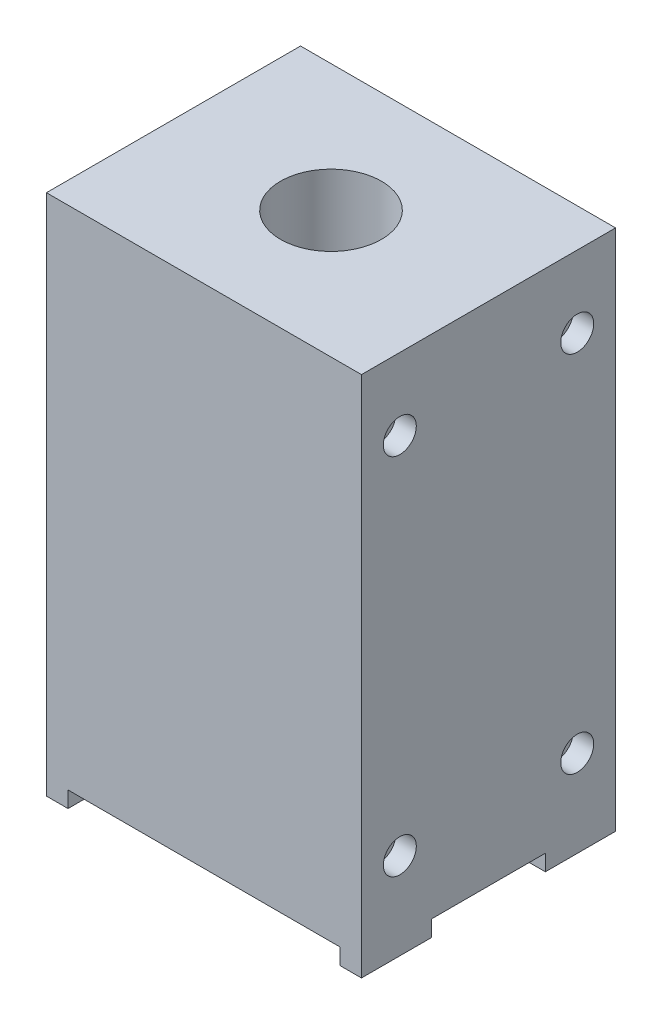
SolidWorks part; units mm, degrees
ref_plane "Front Plane" through (0, 0, 0) normal (0, 0, 1) x (1, 0, 0)
ref_plane "Top Plane" through (0, 0, 0) normal (0, 1, 0) x (1, 0, 0)
ref_plane "Right Plane" through (0, 0, 0) normal (1, 0, 0) x (0, 0, -1)
sketch "Sketch2" plane through (0, 0, 0) normal (0, 1, 0) x (1, 0, 0)
  line L1 (-15.325, 12.36) -> (15.325, 12.36)
  line L2 (-15.325, 12.36) -> (-15.325, -12.36)
  line L3 (-15.325, -12.36) -> (15.325, -12.36)
  line L4 (15.325, 12.36) -> (15.325, -12.36)
  line L5 (-15.325, 12.36) -> (15.325, -12.36) construction
  line L6 (-15.325, -12.36) -> (15.325, 12.36) construction
  point P0 (0, 0)
  dimension "D1" = 24.72
  dimension "D2" = 30.65
extrude "Boss-Extrude1" add sketch "Sketch2" along normal blind 49.27
sketch "Sketch12" plane through (0, 0, 0) normal (0, -1, 0) x (1, 0, 0)
  line L1 (-15.325, 12.36) -> (-13.225, 12.36)
  line L2 (-15.325, 12.36) -> (-15.325, 5.53)
  line L3 (-15.325, 5.53) -> (-13.225, 5.53)
  line L4 (-13.225, 12.36) -> (-13.225, 5.53)
  line L5 (-15.325, -12.36) -> (-13.225, -12.36)
  line L6 (-15.325, -12.36) -> (-15.325, -5.53)
  line L7 (-15.325, -5.53) -> (-13.225, -5.53)
  line L8 (-13.225, -12.36) -> (-13.225, -5.53)
  line L9 (15.325, 12.36) -> (13.225, 12.36)
  line L10 (15.325, 12.36) -> (15.325, 5.53)
  line L11 (15.325, 5.53) -> (13.225, 5.53)
  line L12 (13.225, 12.36) -> (13.225, 5.53)
  line L13 (15.325, -12.36) -> (13.225, -12.36)
  line L14 (15.325, -12.36) -> (15.325, -5.53)
  line L15 (15.325, -5.53) -> (13.225, -5.53)
  line L16 (13.225, -12.36) -> (13.225, -5.53)
  dimension "D1" = 6.83
  dimension "D2" = 6.83
  dimension "D3" = 6.83
  dimension "D4" = 6.83
  dimension "D5" = 2.1
  dimension "D6" = 2.1
  dimension "D7" = 2.1
  dimension "D8" = 2.1
extrude "Boss-Extrude2" add sketch "Sketch12" along normal blind 1.57
sketch "Sketch4" plane through (0, 49.27, 0) normal (0, 1, 0) x (1, 0, 0)
  circle A0 centre (0, 0) radius 4.91
  dimension "D1" = 9.82
extrude "Cut-Extrude3" cut sketch "Sketch4" against normal blind 22
sketch "Sketch5" plane through (0, 27.27, 0) normal (0, 1, 0) x (1, 0, 0)
  circle A0 centre (0, 0) radius 2
  dimension "D1" = 4
extrude "Cut-Extrude4" cut sketch "Sketch5" against normal blind 5
sketch "Sketch7" plane through (0, 22.27, 0) normal (0, 1, 0) x (1, 0, 0)
  circle A0 centre (0, 0) radius 1.5
  dimension "D1" = 3
extrude "Cut-Extrude5" cut sketch "Sketch7" against normal through all
fillet "Fillet4" radius 3 1 edges at (0, 27.27, 2) first distance on face at (0, 27.27, 2)
fillet "Fillet5" radius 3 1 edges at (0, 22.27, 1.5) first distance on face at (0, 22.27, 1.5)
sketch "Sketch13" plane through (15.325, 0, 0) normal (1, 0, 0) x (0, 0, -1)
  line L0 (-12.36, 49.27) -> (12.36, 49.27) construction
  line L1 (-12.36, 49.27) -> (-12.36, -1.57) construction
  line L2 (12.36, 49.27) -> (12.36, -1.57) construction
  line L3 (12.36, -1.57) -> (5.53, -1.57) construction
  line L4 (-5.53, -1.57) -> (-12.36, -1.57) construction
  circle A0 centre (-8.63, 42.27) radius 1.605
  circle A1 centre (8.63, 42.27) radius 1.605
  circle A2 centre (-8.63, 6.87) radius 1.605
  circle A3 centre (8.63, 6.87) radius 1.605
  dimension "D1" = 3.21
  dimension "D2" = 3.21
  dimension "D3" = 3.21
  dimension "D4" = 3.21
  dimension "D5" = 7
  dimension "D6" = 7
  dimension "D7" = 3.73
  dimension "D8" = 3.73
  dimension "D9" = 8.44
  dimension "D10" = 8.44
  dimension "D11" = 3.73
  dimension "D12" = 3.73
extrude "Cut-Extrude6" cut sketch "Sketch13" against normal blind 2
sketch "Sketch14" plane through (15.325, 0, 0) normal (1, 0, 0) x (0, 0, -1)
  line L0 (0, 49.27) -> (0, 0) construction
  line L1 (-12.36, 49.27) -> (12.36, 49.27) construction
equation "\"3。21\"=4.09161"
